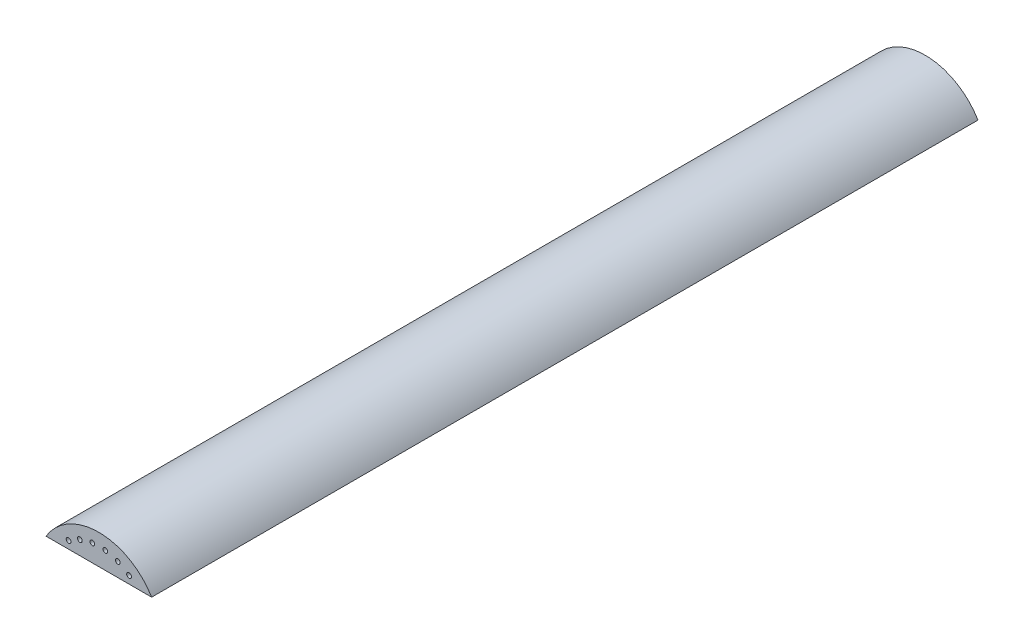
SolidWorks part; units mm, degrees
ref_plane "Front Plane" through (0, 0, 0) normal (0, 0, 1) x (1, 0, 0)
ref_plane "Top Plane" through (0, 0, 0) normal (0, 1, 0) x (1, 0, 0)
ref_plane "Right Plane" through (0, 0, 0) normal (1, 0, 0) x (0, 0, -1)
ref_axis "Axis X" through (-88.99, 0, 0) along (1, 0, 0)
ref_axis "Axis Y" through (0, 55, 0) along (0, -1, 0)
ref_axis "Axis Z" through (0, 0, -88.99) along (0, 0, 1)
sketch "Sketch1" plane through (0, 0, 0) normal (0, 0, 1) x (1, 0, 0)
  line L0 (20.5033, 0) -> (-20.5033, 0) construction
  line L1 (0, -22.8319) -> (0, 22.8319) construction
  line L2 (-19.6898, 0) -> (19.6898, 0)
  arc A0 (-19.6898, 0) -> (19.6898, 0) centre (0, -11.8875) cw
  dimension "D1" = 23
  dimension "D2" = 11.1125
extrude "Boss-Extrude1" add sketch "Sketch1" along normal blind 308
sketch "Sketch2" plane through (0, 0, 308) normal (0, 0, 1) x (1, 0, 0)
  line L0 (0, -6.1119) -> (0, 6.1119) construction
  line L2 (-19.6898, 0) -> (19.6898, 0) construction
  circle A1 centre (-11.2697, 2.7995) radius 0.889
  circle A7 centre (-7.0844, 5.2158) radius 0.889
  circle A8 centre (-2.4164, 6.4666) radius 0.889
  circle A9 centre (2.4164, 6.4666) radius 0.889
  circle A10 centre (7.0844, 5.2158) radius 0.889
  circle A11 centre (11.2697, 2.7995) radius 0.889
  circle A12 centre (0, -11.8876) radius 18.5126 construction
  dimension "D3" = 1.778
  dimension "D4" = 4.6681
  dimension "D7" = 4.1853
  dimension "D1" = 2.4164
  dimension "D2" = 6.4666
  dimension "D5" = 5.2158
  dimension "D6" = 2.7995
extrude "Cut-Extrude1" cut sketch "Sketch2" against normal up to next
